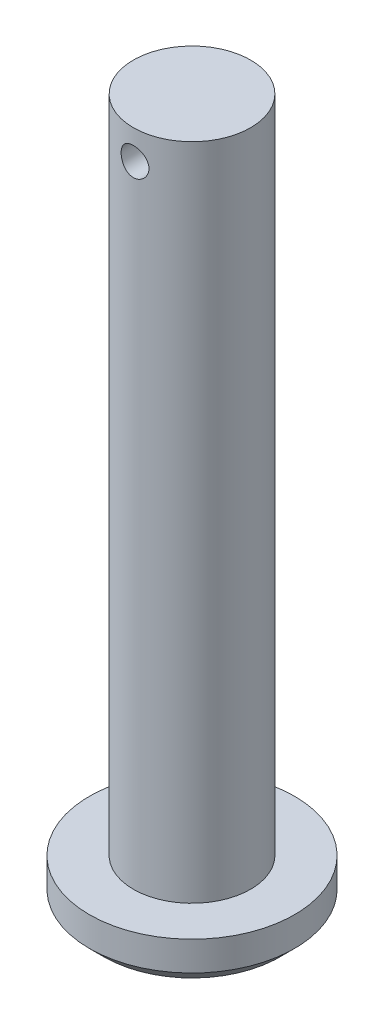
SolidWorks part; units mm, degrees
ref_plane "Front Plane" through (0, 0, 0) normal (0, 0, 1) x (1, 0, 0)
ref_plane "Top Plane" through (0, 0, 0) normal (0, 1, 0) x (1, 0, 0)
ref_plane "Right Plane" through (0, 0, 0) normal (1, 0, 0) x (0, 0, -1)
sketch "Sketch1" plane through (0, 0, 0) normal (0, 1, 0) x (1, 0, 0)
  circle A0 centre (0, 0) radius 7
  circle A1 centre (0, 0) radius 4
  dimension "D1" = 14
  dimension "D2" = 8
extrude "Boss-Extrude1" add sketch "Sketch1" against normal blind 3 contours A0
extrude "Boss-Extrude2" add sketch "Sketch1<3>" along normal blind 45 contours A1
sketch "Sketch1<3>" plane through (0, 0, 0) normal (0, 1, 0) x (1, 0, 0) same geometry as "Sketch1"
chamfer "Chamfer1" distance 1 angle 45 1 edges at (0, -3, 7)
ref_plane "Plane1" through (0, 0, 4) normal (0, 0, 1) x (1, 0, 0)
sketch "Sketch2" plane through (0, 0, 4) normal (0, 0, 1) x (1, 0, 0)
  line L0 (4, 45) -> (-4, 45) construction
  circle A0 centre (0, 43) radius 0.95
  point P4 (0, 0)
  dimension "D2" = 1.9
  dimension "D1" = 2
extrude "Cut-Extrude1" cut sketch "Sketch2" against normal up to next contours A0
